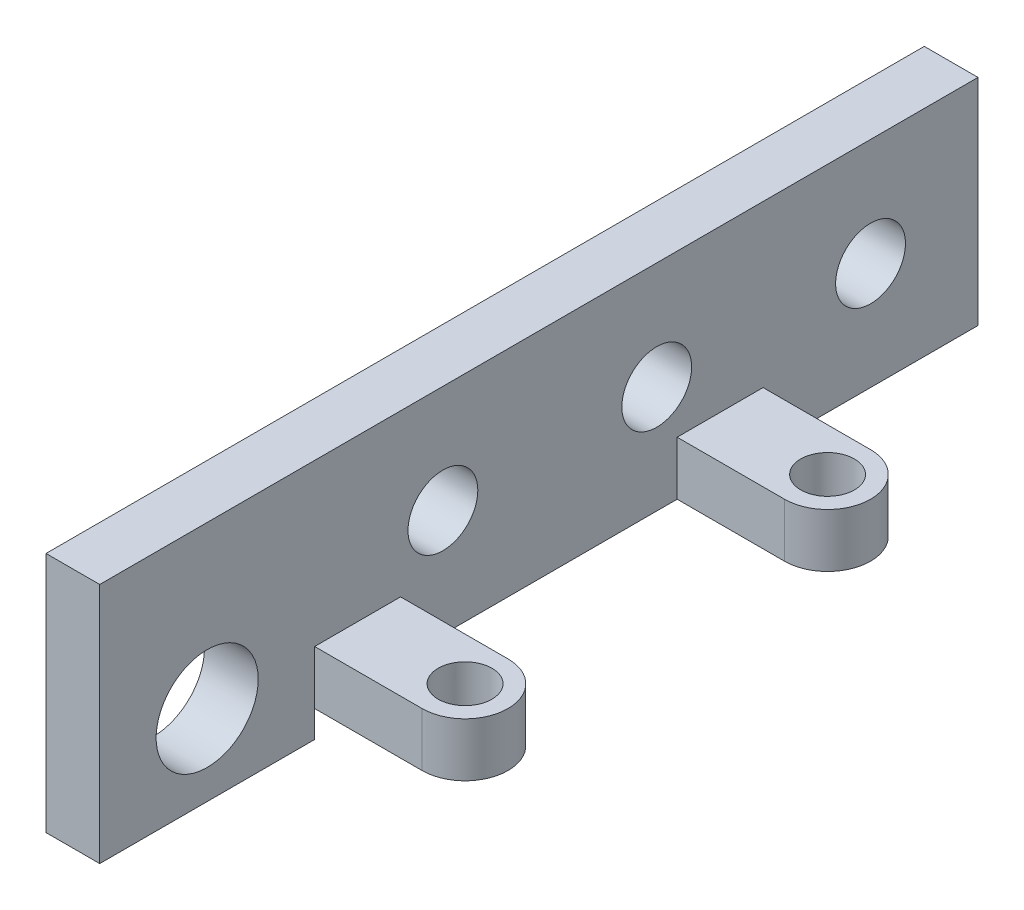
SolidWorks part; units mm, degrees
ref_plane "Front Plane" through (0, 0, 0) normal (0, 0, 1) x (1, 0, 0)
ref_plane "Top Plane" through (0, 0, 0) normal (0, 1, 0) x (1, 0, 0)
ref_plane "Right Plane" through (0, 0, 0) normal (1, 0, 0) x (0, 0, -1)
sketch "Sketch1" plane through (0, 0, 0) normal (1, 0, 0) x (0, 0, -1)
  line L0 (-81.7374, 0) -> (-81.7374, -2.5)
  line L1 (0, 0) -> (-81.7374, 0)
  line L2 (0, 0) -> (0, 20)
  line L3 (0, 20) -> (-81.7374, 20)
  line L4 (-81.7374, 0) -> (-81.7374, 20)
  line L5 (-81.7374, -2.5) -> (-71.7374, -2.5)
  line L6 (-71.7374, -2.5) -> (-61.7374, -2.5)
  line L7 (-61.7374, -2.5) -> (-61.7374, 0)
  circle A0 centre (-29.9, 10) radius 3.25
  circle A1 centre (-49.8, 10) radius 3.25
  circle A2 centre (-71.7374, 5) radius 4.75
  circle A3 centre (-10, 10) radius 3.25
  point P11 (0, 0)
  dimension "D1" = 10
  dimension "D3" = 6.5
  dimension "D4" = 10
  dimension "D10" = 9.5
  dimension "D2" = 20
  dimension "D5" = 22.5
  dimension "D6" = 19.9
  dimension "D7" = 10
  dimension "D8" = 5
  dimension "D9" = 19.9
  dimension "D11" = 2.5
extrude "Boss-Extrude1" add sketch "Sketch1" along normal blind 5 contours L4 L1 L2 L3 A3 A2 A1 A0 | L6 L7 L1 L0 L5 region at (0, -1.25, 71.7374) region at (0, 10.242, 40.1202)
sketch "Sketch2" plane through (5, 0, 0) normal (1, 0, 0) x (0, 0, -1)
  line L0 (0, 0) -> (-40.8687, 0) construction
  line L1 (0, 0) -> (-61.7374, 0) construction
  line L2 (-81.7374, -2.5) -> (-81.7374, 20) construction
  line L3 (-40.8687, 0) -> (-40.8687, 20) construction
  line L6 (-61.7374, 0) -> (-53.7374, 0)
  line L7 (-61.7374, 0) -> (-61.7374, 5)
  line L8 (-61.7374, 5) -> (-53.7374, 5)
  line L9 (-53.7374, 5) -> (-53.7374, 0)
  line L10 (-40.8687, 0) -> (-81.7374, 0) construction
  line L11 (0, 20) -> (-81.7374, 20) construction
  line L12 (-20, 5) -> (-28, 5)
  line L15 (-20, 0) -> (-20, 5)
  line L16 (-20, 0) -> (-28, 0)
  line L17 (-28, 5) -> (-28, 0)
  point P5 (0, 0)
  point P7 (0, 0)
  point P14 (0, 0)
  dimension "D5" = 8
  dimension "D6" = 5
extrude "Boss-Extrude2" add sketch "Sketch2" along normal blind 10 contours L9 L6 L7 L8 | L12 L17 L16 L15
sketch "Sketch3" plane through (0, 5, 0) normal (0, 1, 0) x (1, 0, 0)
  line L0 (15, -53.7374) -> (15, -61.7374)
  arc A0 (15, -53.7374) -> (15, -61.7374) centre (15, -57.7374) cw
  circle A1 centre (15, -57.7374) radius 2.5
  dimension "D1" = 5
extrude "Boss-Extrude3" add sketch "Sketch3" against normal blind 5 contours A0 L0
extrude "Cut-Extrude2" cut sketch "Sketch3<6>" against normal through all contours A1
sketch "Sketch3<6>" plane through (0, 5, 0) normal (0, 1, 0) x (1, 0, 0) same geometry as "Sketch3"
ref_plane "Plane1" through (0, 0, 40.8687) normal (0, 0, 1) x (1, 0, 0)
mirror "Mirror1" about plane through (0, 0, 40.8687) normal (0, 0, 1) of "Boss-Extrude3", "Cut-Extrude2"
